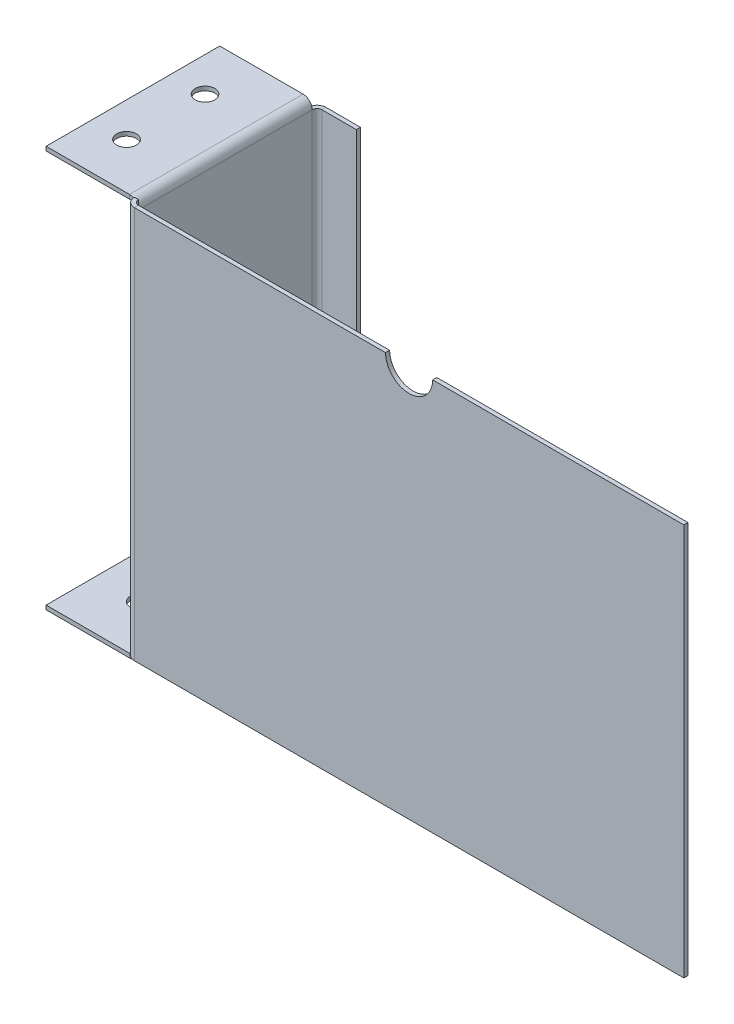
SolidWorks part; units mm, degrees
note: The reader was unsure of these and kept them because the rebuilt part matched: flange length of "Edge-Flange1", "Edge-Flange2", "Edge-Flange3", "Edge-Flange4".
material "Plain Carbon Steel"
ref_plane "Front Plane" through (0, 0, 0) normal (0, 0, 1) x (1, 0, 0)
ref_plane "Top Plane" through (0, 0, 0) normal (0, 1, 0) x (1, 0, 0)
ref_plane "Right Plane" through (0, 0, 0) normal (1, 0, 0) x (0, 0, -1)
sketch "Sketch1" plane through (0, 0, 0) normal (0, 0, 1) x (1, 0, 0)
  line L0 (193.04, 254) -> (355.6, 254)
  line L1 (0, 0) -> (355.6, 0)
  line L2 (0, 0) -> (0, 254)
  line L3 (0, 254) -> (162.56, 254)
  line L4 (355.6, 0) -> (355.6, 254)
  line L5 (162.56, 254) -> (193.04, 254) construction
  line L6 (177.8, 0) -> (177.8, 254) construction
  line L7 (0, 76.2) -> (355.6, 76.2) construction
  arc A0 (162.56, 254) -> (193.04, 254) centre (177.8, 254) ccw
  dimension "D3" = 15.24
  dimension "D1" = 355.6
  dimension "D2" = 254
  dimension "D4" = 177.8
base flange "Base-Flange1" sketch "Sketch1" thickness 2.6568 reverse thickness direction no parameters "D1"=3.175
edge flange "Edge-Flange1" sketch "Sketch8" flange angle 90 flange length 115.57 flange position bend outside bend radius 3.175 thickness 2.6568 relief rectangular parameters "D6"=10
sketch "Sketch8" plane through (0, 0, -2.6568) normal (-1, 0, 0) x (0, 1, 0)
  line L0 (254, 0) -> (0, 0) construction
  line L1 (254, 0) -> (0, 0)
  line L2 (0, 0) -> (0, 115.57)
  line L3 (0, 115.57) -> (254, 115.57)
  line L4 (254, 115.57) -> (254, 0)
bend "EdgeBend1" bend radius 3.175 bend angle 90 parameters "D5"=1
edge flange "Edge-Flange2" sketch "Sketch11" flange angle 90 flange length 57.15 flange position material inside bend radius 3.175 thickness 2.6568 relief none parameters "D6"=10
sketch "Sketch11" plane through (-5.8318, 254, 0) normal (0, 1, 0) x (0, 0, -1)
  line L0 (5.8318, 0) -> (118.2268, 0) construction
  line L1 (5.8318, 0) -> (118.2268, 0)
  line L2 (5.8318, 0) -> (5.8318, 57.15)
  line L3 (5.8318, 57.15) -> (118.2268, 57.15)
  line L4 (118.2268, 57.15) -> (118.2268, 0)
bend "EdgeBend2" bend radius 3.175 bend angle 90 parameters "D5"=2
edge flange "Edge-Flange3" sketch "Sketch14" flange angle 90 flange length 57.15 flange position bend outside bend radius 3.175 thickness 2.6568 relief rectangular parameters "D6"=10
sketch "Sketch14" plane through (-5.8318, 0, 0) normal (0, -1, 0) x (0, 0, 1)
  line L0 (-118.2268, 0) -> (-5.8318, 0) construction
  line L1 (-118.2268, 0) -> (-5.8318, 0)
  line L2 (-118.2268, 0) -> (-118.2268, 57.15)
  line L3 (-118.2268, 57.15) -> (-5.8318, 57.15)
  line L4 (-5.8318, 57.15) -> (-5.8318, 0)
bend "EdgeBend3" bend radius 3.175 bend angle 90 parameters "D5"=3
edge flange "Edge-Flange4" sketch "Sketch17" flange angle 90 flange length 25.4 flange position bend outside bend radius 3.175 thickness 2.6568 relief rectangular parameters "D6"=10
sketch "Sketch17" plane through (-3.175, 0, -118.2268) normal (0, 0, 1) x (0, -1, 0)
  line L2 (-248.1682, 0) -> (-248.1682, 25.4)
  line L3 (-248.1682, 25.4) -> (0, 25.4)
  line L4 (0, 25.4) -> (0, 0)
  line L5 (0, 0) -> (-248.1682, 0) construction
  line L6 (0, 0) -> (-248.1682, 0)
bend "EdgeBend4" bend radius 3.175 bend angle 90 parameters "D5"=4
sketch "Sketch23" plane through (0, 254, 0) normal (0, 1, 0) x (1, 0, 0)
  line L0 (-62.9818, 118.2268) -> (-62.9818, 5.8318) construction
  line L1 (-9.0068, 118.2268) -> (-62.9818, 118.2268) construction
  circle A0 centre (-40.7645, 86.4768) radius 6.35
  circle A1 centre (-40.7645, 35.6768) radius 6.35
  dimension "D5" = 12.7
  dimension "D1" = 22.2174
  dimension "D2" = 22.2174
  dimension "D3" = 31.75
  dimension "D4" = 50.8
extrude "Cut-Extrude1" cut sketch "Sketch23" along direction (0, -1, 0) on the side against the normal up to next (2.6568 mm away) normal cut yes
sketch "Sketch24" plane through (0, -3.175, 0) normal (0, 1, 0) x (1, 0, 0)
  line L0 (-34.4068, 118.2268) -> (-34.4068, 82.6668) construction
  line L3 (-62.9818, 118.2268) -> (-9.0068, 118.2268) construction
  line L4 (-34.4068, 82.6668) -> (-34.4068, 38.2168) construction
  line L5 (-34.4068, 38.2168) -> (-34.4068, 5.8318) construction
  line L6 (-9.0068, 5.8318) -> (-62.9818, 5.8318) construction
  line L8 (-9.0068, 118.2268) -> (-9.0068, 5.8318) construction
  circle A0 centre (-34.4068, 82.6668) radius 6.35
  circle A1 centre (-34.4068, 38.2168) radius 6.35
  dimension "D1" = 12.7
  dimension "D2" = 44.45
  dimension "D3" = 25.4
  dimension "D4" = 32.385
extrude "Cut-Extrude2" cut sketch "Sketch24" along direction (0, 1, 0) on the side against the normal up to next (2.6568 mm away) normal cut yes
sketch "Sketch26" plane through (0, 0, -2.6568) normal (0, 0, -1) x (-1, 0, 0)
  line L0 (-177.8, 254) -> (-177.8, 0) construction
  line L1 (0, 0) -> (-355.6, 0) construction
  line L2 (-355.6, 76.2) -> (0, 76.2) construction
  line L3 (-355.6, 0) -> (-355.6, 254) construction
  line L4 (0, 254) -> (0, 0) construction
  line L5 (-355.6, 254) -> (-193.04, 254) construction
  dimension "D1" = 177.8
sketch "Sketch27" plane through (-5.8318, 0, 0) normal (-1, 0, 0) x (0, 0, 1)
  line L0 (-62.0293, 248.1682) -> (-62.0293, 76.2) construction
  line L1 (-118.2268, 248.1682) -> (-5.8318, 248.1682) construction
  line L2 (-62.0293, 76.2) -> (-62.0293, 41.7932) construction
  line L3 (-118.2268, 41.7932) -> (-5.8318, 41.7932) construction
  line L4 (-118.2268, 248.1682) -> (-118.2268, 0) construction
  line L5 (-5.8318, 248.1682) -> (-5.8318, 0) construction
  line L8 (-118.2268, 254) -> (-5.8318, 254) construction
  circle A0 centre (-86.7766, 41.7932) radius 6.35
  circle A1 centre (-34.1884, 41.7932) radius 6.35
  dimension "D3" = 12.7
  dimension "D1" = 177.8
  dimension "D2" = 34.4068
  dimension "D4" = 31.4503
  dimension "D5" = 52.5882
extrude "Cut-Extrude3" cut sketch "Sketch27" along direction (1, 0, 0) on the side against the normal up to next (2.6568 mm away) normal cut yes
sketch "Bend-Lines1" [suppressed] plane through (0, 0, 0) normal (0, 1, 0) x (1, 0, 0)
sketch "Bounding-Box1" [suppressed] plane through (0, 0, 0) normal (0, 1, 0) x (1, 0, 0)
sheet metal parameters "Sheet-Metal1" thickness 2.6568 parameters "D1"=3.175
flat pattern "Flat-Pattern1" [suppressed]
sketch "Bend-Lines2" plane through (0, 0, 0) normal (0, 1, 0) x (1, 0, 0)
sketch3d "Bounding-Box2" [suppressed]
  line L0 (0, 0, 0) -> (-355.6, 0, 0) construction
  line L1 (0, 254, 0) -> (-355.6, 254, 0) construction
  line L2 (0, 0, 0) -> (0, 254, 0) construction
  line L3 (-355.6, 0, 0) -> (-355.6, 254, 0) construction
sheet metal parameters "Sheet-Metal2" thickness 2.6568 parameters "D1"=3.175
flat pattern "Flat-Pattern1"
sketch "Bend-Lines2" plane through (0, 0, 0) normal (0, 0, 1) x (1, 0, 0)
  line L0 (-3.537, 254) -> (-3.537, 0) construction
  line L1 (-3.537, 254) -> (-3.537, 0) construction
sketch3d "Bounding-Box2" [suppressed]
  line L0 (-123.5965, 0, 0) -> (355.6, 0, 0) construction
  line L1 (-123.5965, 254, 0) -> (355.6, 254, 0) construction
  line L2 (-123.5965, 0, 0) -> (-123.5965, 254, 0) construction
  line L3 (355.6, 0, 0) -> (355.6, 254, 0) construction
bend of the flat pattern "Flatten-<EdgeBend1>1"
sheet metal parameters "Sheet-Metal3" thickness 2.6568 parameters "D1"=3.175
flat pattern "Flat-Pattern1"
sketch "Bend-Lines2" plane through (0, 0, 0) normal (0, 0, 1) x (1, 0, 0)
  line L0 (-3.537, 254) -> (-3.537, 0) construction
  line L1 (-3.537, 254) -> (-3.537, 0) construction
  line L2 (-7.074, 251.7051) -> (-123.5965, 251.7051) construction
  line L3 (-7.074, 251.7051) -> (-123.5965, 251.7051) construction
sketch3d "Bounding-Box2" [suppressed]
  line L0 (-123.5965, 0, 0) -> (355.6, 0, 0) construction
  line L1 (-123.5965, 309.2171, 0) -> (355.6, 309.2171, 0) construction
  line L2 (-123.5965, 0, 0) -> (-123.5965, 309.2171, 0) construction
  line L3 (355.6, 0, 0) -> (355.6, 309.2171, 0) construction
bend of the flat pattern "Flatten-<EdgeBend1>1"
bend of the flat pattern "Flatten-<EdgeBend2>1"
sheet metal parameters "Sheet-Metal4" thickness 2.6568 parameters "D1"=3.175
flat pattern "Flat-Pattern1"
sketch "Bend-Lines2" plane through (0, 0, 0) normal (0, 0, 1) x (1, 0, 0)
  line L0 (-3.537, 254) -> (-3.537, 0) construction
  line L1 (-3.537, 254) -> (-3.537, 0) construction
  line L2 (-7.074, 251.7051) -> (-123.5965, 251.7051) construction
  line L3 (-7.074, 251.7051) -> (-123.5965, 251.7051) construction
  line L4 (-123.5965, -3.537) -> (-7.074, -3.537) construction
  line L5 (-123.5965, -3.537) -> (-7.074, -3.537) construction
sketch3d "Bounding-Box2" [suppressed]
  line L0 (-123.5965, -61.049, 0) -> (355.6, -61.049, 0) construction
  line L1 (-123.5965, 309.2171, 0) -> (355.6, 309.2171, 0) construction
  line L2 (-123.5965, -61.049, 0) -> (-123.5965, 309.2171, 0) construction
  line L3 (355.6, -61.049, 0) -> (355.6, 309.2171, 0) construction
bend of the flat pattern "Flatten-<EdgeBend1>1"
bend of the flat pattern "Flatten-<EdgeBend2>1"
bend of the flat pattern "Flatten-<EdgeBend3>1"
sheet metal parameters "Sheet-Metal5" thickness 2.6568 parameters "D1"=3.175
flat pattern "Flat-Pattern1" [suppressed]
sketch "Bend-Lines2" plane through (0, 0, 0) normal (0, 0, 1) x (1, 0, 0)
  line L0 (-3.537, 254) -> (-3.537, 0) construction
  line L1 (-3.537, 254) -> (-3.537, 0) construction
  line L2 (-7.074, 251.7051) -> (-119.469, 251.7051) construction
  line L3 (-7.074, 251.7051) -> (-119.469, 251.7051) construction
  line L4 (-119.469, -3.537) -> (-7.074, -3.537) construction
  line L5 (-119.469, -3.537) -> (-7.074, -3.537) construction
  line L6 (-123.0059, 248.1682) -> (-123.0059, 0) construction
  line L7 (-123.0059, 248.1682) -> (-123.0059, 0) construction
sketch3d "Bounding-Box2" [suppressed]
  line L0 (-326.5679, -315.049, 0) -> (177.8, -315.049, 0) construction
  line L1 (-326.5679, 55.2171, 0) -> (177.8, 55.2171, 0) construction
  line L2 (-326.5679, -315.049, 0) -> (-326.5679, 55.2171, 0) construction
  line L3 (177.8, -315.049, 0) -> (177.8, 55.2171, 0) construction
bend of the flat pattern "Flatten-<EdgeBend1>1"
bend of the flat pattern "Flatten-<EdgeBend2>1"
bend of the flat pattern "Flatten-<EdgeBend3>1"
bend of the flat pattern "Flatten-<EdgeBend4>1"
sketch "Sketch18-1" [suppressed] plane through (-1.2421, 246.2353, 0) normal (0, 0, 1) x (0, -1, 0)
  spline S2 degree 3 poles (-47.1137, -86.4768) (-47.1137, -99.1768) (-34.4137, -99.1768) (-34.4137, -86.4768) (-34.4137, -73.7768) (-47.1137, -73.7768) (-47.1137, -86.4768) (-47.1137, -99.1768) (-34.4137, -99.1768) knots -0.5 0 0 0 0.5 0.5 0.5 1 1 1 1.5 1.5 1.5 weights 1 0.333333 0.333333 1 0.333333 0.333333 1 0.333333 0.333333 only from (-47.1137, -86.4768) to (-47.1137, -86.4768)
  spline S3 degree 3 poles (-47.1137, -34.4068) (-47.1137, -47.1068) (-34.4137, -47.1068) (-34.4137, -34.4068) (-34.4137, -21.7068) (-47.1137, -21.7068) (-47.1137, -34.4068) (-47.1137, -47.1068) (-34.4137, -47.1068) knots -0.5 0 0 0 0.5 0.5 0.5 1 1 1 1.5 1.5 1.5 weights 1 0.333333 0.333333 1 0.333333 0.333333 1 0.333333 0.333333 only from (-47.1137, -34.4068) to (-47.1137, -34.4068)
sheet metal parameters "Sheet-Metal8" thickness 2.6568 parameters "D1"=3.175
flat pattern "Flat-Pattern1"
sketch "Bend-Lines2" plane through (0, 0, 0) normal (0, 0, 1) x (1, 0, 0)
  line L0 (-3.537, 254) -> (-3.537, 0) construction
  line L1 (-3.537, 254) -> (-3.537, 0) construction
  line L2 (-7.074, 251.7051) -> (-119.469, 251.7051) construction
  line L3 (-7.074, 251.7051) -> (-119.469, 251.7051) construction
  line L4 (-119.469, -3.537) -> (-7.074, -3.537) construction
  line L5 (-119.469, -3.537) -> (-7.074, -3.537) construction
  line L6 (-123.0059, 248.1682) -> (-123.0059, 0) construction
  line L7 (-123.0059, 248.1682) -> (-123.0059, 0) construction
sketch3d "Bounding-Box2" [suppressed]
  line L0 (-326.5679, -315.049, 0) -> (177.8, -315.049, 0) construction
  line L1 (-326.5679, 55.2171, 0) -> (177.8, 55.2171, 0) construction
  line L2 (-326.5679, -315.049, 0) -> (-326.5679, 55.2171, 0) construction
  line L3 (177.8, -315.049, 0) -> (177.8, 55.2171, 0) construction
bend of the flat pattern "Flatten-<EdgeBend1>1"
bend of the flat pattern "Flatten-<EdgeBend2>1"
bend of the flat pattern "Flatten-<EdgeBend3>1"
bend of the flat pattern "Flatten-<EdgeBend4>1"
sheet metal parameters "Sheet-Metal9" thickness 2.6568 parameters "D1"=3.175
flat pattern "Flat-Pattern1"
sketch "Bend-Lines2" plane through (0, 0, 0) normal (0, 0, 1) x (1, 0, 0)
  line L0 (-3.537, 254) -> (-3.537, 0) construction
  line L1 (-3.537, 254) -> (-3.537, 0) construction
  line L2 (-7.074, 251.7051) -> (-119.469, 251.7051) construction
  line L3 (-7.074, 251.7051) -> (-119.469, 251.7051) construction
  line L4 (-119.469, -3.537) -> (-7.074, -3.537) construction
  line L5 (-119.469, -3.537) -> (-7.074, -3.537) construction
  line L6 (-123.0059, 248.1682) -> (-123.0059, 0) construction
  line L7 (-123.0059, 248.1682) -> (-123.0059, 0) construction
sketch3d "Bounding-Box2" [suppressed]
  line L0 (-326.5679, -315.049, 0) -> (177.8, -315.049, 0) construction
  line L1 (-326.5679, 55.2171, 0) -> (177.8, 55.2171, 0) construction
  line L2 (-326.5679, -315.049, 0) -> (-326.5679, 55.2171, 0) construction
  line L3 (177.8, -315.049, 0) -> (177.8, 55.2171, 0) construction
bend of the flat pattern "Flatten-<EdgeBend1>1"
bend of the flat pattern "Flatten-<EdgeBend2>1"
bend of the flat pattern "Flatten-<EdgeBend3>1"
bend of the flat pattern "Flatten-<EdgeBend4>1"
sheet metal parameters "Sheet-Metal10" thickness 2.6568 parameters "D1"=3.175
flat pattern "Flat-Pattern1"
sketch "Bend-Lines2" plane through (0, 0, 0) normal (0, 0, 1) x (1, 0, 0)
  line L0 (-3.537, 254) -> (-3.537, 0) construction
  line L1 (-3.537, 254) -> (-3.537, 0) construction
  line L2 (-7.074, 251.7051) -> (-119.469, 251.7051) construction
  line L3 (-7.074, 251.7051) -> (-119.469, 251.7051) construction
  line L4 (-119.469, -3.537) -> (-7.074, -3.537) construction
  line L5 (-119.469, -3.537) -> (-7.074, -3.537) construction
  line L6 (-123.0059, 248.1682) -> (-123.0059, 0) construction
  line L7 (-123.0059, 248.1682) -> (-123.0059, 0) construction
sketch3d "Bounding-Box2" [suppressed]
  line L0 (-326.5679, -315.049, 0) -> (177.8, -315.049, 0) construction
  line L1 (-326.5679, 55.2171, 0) -> (177.8, 55.2171, 0) construction
  line L2 (-326.5679, -315.049, 0) -> (-326.5679, 55.2171, 0) construction
  line L3 (177.8, -315.049, 0) -> (177.8, 55.2171, 0) construction
bend of the flat pattern "Flatten-<EdgeBend1>1"
bend of the flat pattern "Flatten-<EdgeBend2>1"
bend of the flat pattern "Flatten-<EdgeBend3>1"
bend of the flat pattern "Flatten-<EdgeBend4>1"
